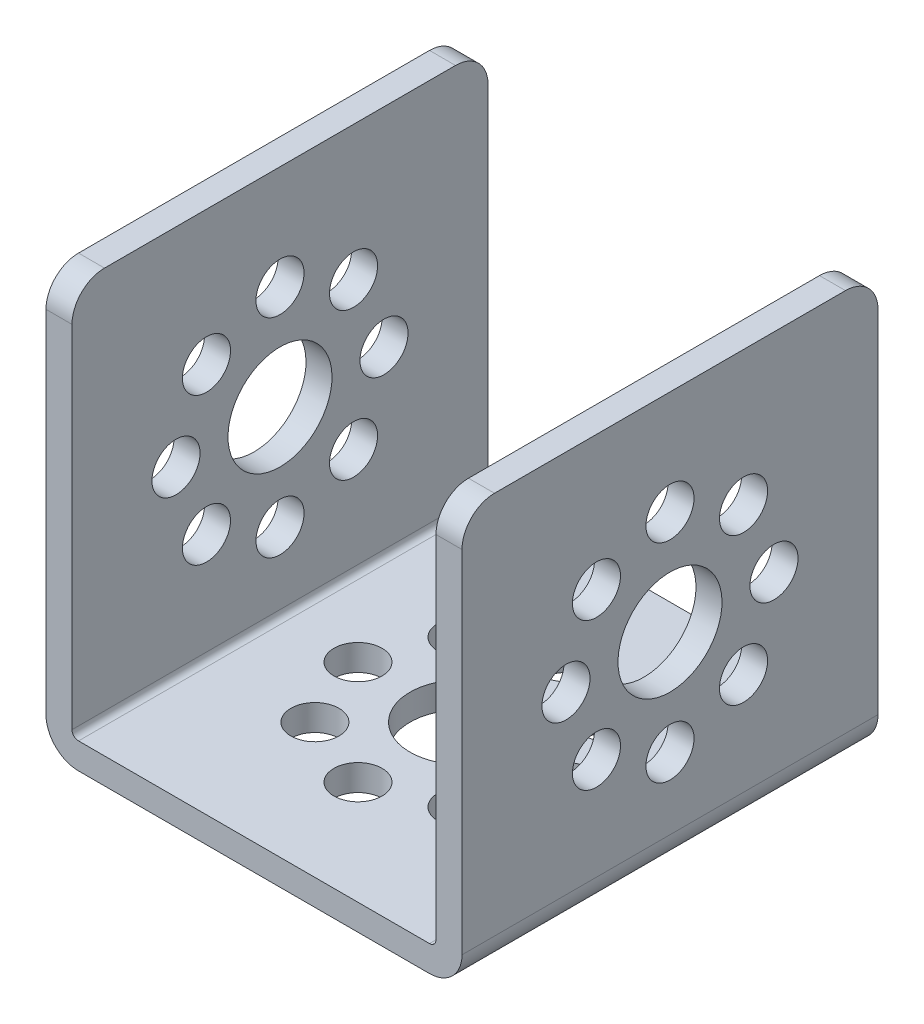
SolidWorks part; units mm, degrees
note: The reader was unsure of these and kept them because the rebuilt part matched: shared geometry of "Sketch3<3>", "Sketch2<4>".
material "5052 Alloy"
ref_plane "Front Plane" through (0, 0, 0) normal (0, 0, 1) x (1, 0, 0)
ref_plane "Top Plane" through (0, 0, 0) normal (0, 1, 0) x (1, 0, 0)
ref_plane "Right Plane" through (0, 0, 0) normal (1, 0, 0) x (0, 0, -1)
sketch "Sketch1" plane through (0, 0, 0) normal (0, 0, 1) x (1, 0, 0)
  line L0 (-13.5, 0) -> (13.5, 0)
  line L1 (16, 2.5) -> (16, 32)
  line L2 (16, 32) -> (14, 32)
  line L3 (14, 32) -> (14, 2.5)
  line L4 (13.5, 2) -> (-13.5, 2)
  line L5 (-14, 2.5) -> (-14, 32)
  line L6 (-14, 32) -> (-16, 32)
  line L7 (-16, 32) -> (-16, 2.5)
  arc A0 (-16, 2.5) -> (-13.5, 0) centre (-13.5, 2.5) ccw
  arc A1 (16, 2.5) -> (13.5, 0) centre (13.5, 2.5) cw
  arc A2 (14, 2.5) -> (13.5, 2) centre (13.5, 2.5) cw
  arc A3 (-13.5, 2) -> (-14, 2.5) centre (-13.5, 2.5) cw
  point P14 (16, 0)
  point P17 (14, 2)
  dimension "D7" = 2.5
  dimension "D8" = 0.5
  dimension "D1" = 32
  dimension "D2" = 2
  dimension "D3" = 2
  dimension "D4" = 2
  dimension "D5" = 32
  dimension "D6" = 32
extrude "Extrude1" add sketch "Sketch1" along normal mid plane 32
fillet "Fillet1" radius 2.5
sketch "Sketch2" plane through (0, 0, 0) normal (0, -1, 0) x (1, 0, 0)
  line B0 (0, 0) -> (8, 0) construction
  circle B1 centre (0, 0) radius 4
  circle B2 centre (8, 0) radius 1.85
  circle B3 centre (0, 0) radius 8 construction
sketch_block_instance "Block-Tetrix Hole Pattern - 8x8x3.7-1"
sketch_block "Block-Tetrix Hole Pattern - 8x8x3.7" parameters "D1"=3.7, "D2"=8, "D3"=16
extrude "Cut-Extrude1" cut sketch "Sketch2" against normal through all contours B1
sketch "Sketch3" plane through (-16, 0, 0) normal (-1, 0, 0) x (0, 0, 1)
  line L0 (13.5, 32) -> (-13.5, 32) construction
  line B0 (0, 16) -> (0, 8) construction
  circle B1 centre (0, 16) radius 4
  circle B2 centre (0, 8) radius 1.85
  circle B3 centre (0, 16) radius 8 construction
  dimension "D1" = 16
sketch_block_instance "Block-Tetrix Hole Pattern - 8x8x3.7-4"
extrude "Cut-Extrude3" cut sketch "Sketch3" against normal through all contours B1
extrude "Cut-Extrude4" cut sketch "Sketch3<3>" against normal through all contours B2
sketch "Sketch3<3>" plane through (-16, 0, 0) normal (-1, 0, 0) x (0, 0, 1) same geometry as "Sketch3"
extrude "Cut-Extrude2" cut sketch "Sketch2<4>" against normal through all contours B2
sketch "Sketch2<4>" plane through (0, 0, 0) normal (0, -1, 0) x (1, 0, 0) same geometry as "Sketch2"
pattern_circular "CirPattern1" count 8 over 360 about axis through (0, 0, 0) along (0, 1, 0) of "Cut-Extrude2"
pattern_circular "CirPattern3" count 8 over 360 about axis through (0, 16, 0) along (1, 0, 0) of "Cut-Extrude4"
